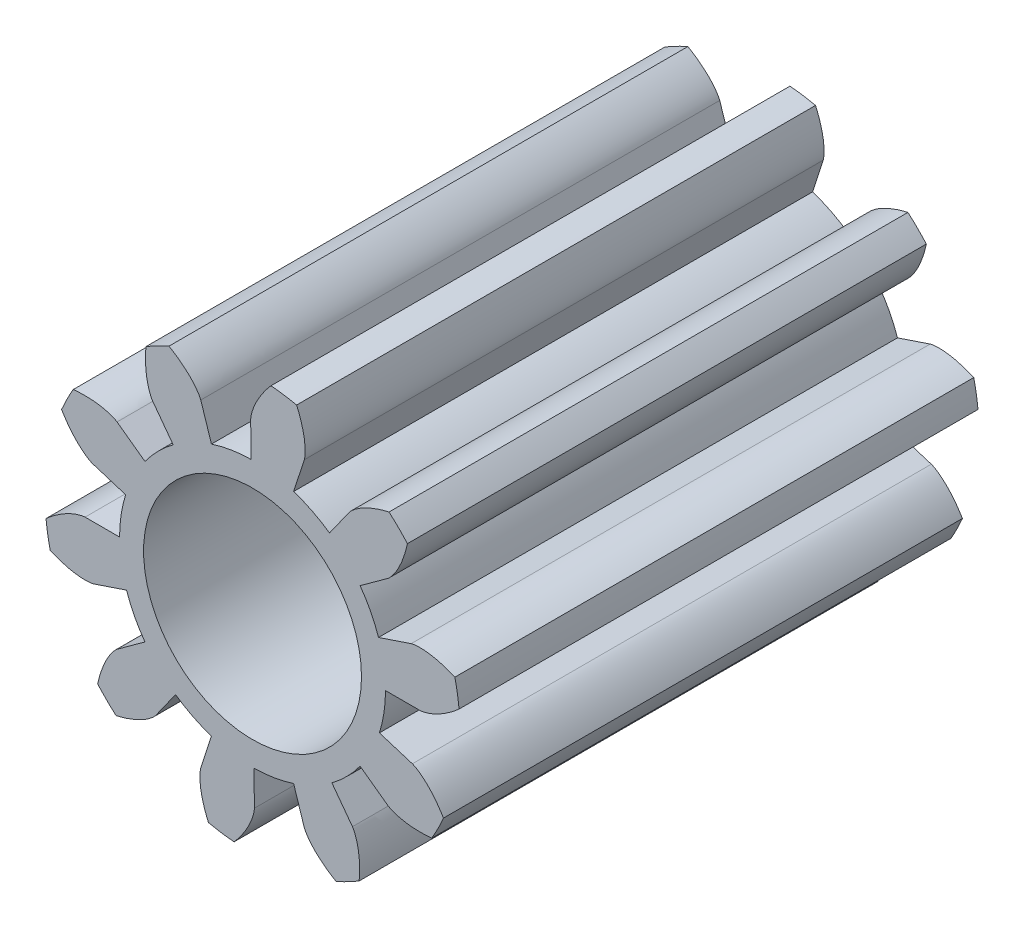
SolidWorks part; units mm, degrees
note: '?' marks a value the reader was unsure of. The reader was unsure of these and kept them because the rebuilt part matched: shared geometry of "Sketch1<7>".
material "AISI 4130 Steel, normalized at 870C"
ref_plane "Front Plane" through (0, 0, 0) normal (0, 0, 1) x (1, 0, 0)
ref_plane "Top Plane" through (0, 0, 0) normal (0, 1, 0) x (1, 0, 0)
ref_plane "Right Plane" through (0, 0, 0) normal (1, 0, 0) x (0, 0, -1)
sketch "Sketch1" plane through (0, 0, 0) normal (0, 0, 1) x (1, 0, 0)
  line L0 (6.1477, 0) -> (4.8806, 0)
  line L1 (7.5195, 1.2338) -> (-7.5195, -1.2338)
  line L2 (0, 0) -> (6.3499, 0.0352) construction
  circle A0 centre (0, 0) radius 6.1477 construction
  circle A1 centre (0, 0) radius 7.62
  circle A2 centre (0, 0) radius 4.8806
  circle A3 centre (0, 0) radius 6.35 construction
  spline S0 degree 4 poles (6.1477, 0) (6.1523, 0.0001) (6.165, 0.0007) (6.189, 0.0029) (6.2281, 0.0082) (6.2775, 0.0175) (6.341, 0.0322) (6.415, 0.053) (6.4955, 0.0796) (6.5819, 0.1125) (6.6671, 0.1487) (6.7509, 0.188) (6.8333, 0.23) (6.9318, 0.2841) (7.0479, 0.3536) (7.1805, 0.4412) (7.3269, 0.548) (7.4716, 0.6647) (7.6101, 0.7858) (7.7452, 0.9151) (7.8725, 1.0451) (7.9994, 1.187) (8.1138, 1.3213) (8.2358, 1.479) (8.3325, 1.6083) (8.453, 1.7861) (8.5222, 1.8932) (8.6005, 2.0209) (8.634, 2.0789) (8.6547, 2.1145) knots 0 0 0 0 0 0.005377 0.015084 0.028532 0.04661 0.064855 0.092111 0.119476 0.146842 0.174209 0.201575 0.228941 0.256307 0.307035 0.361767 0.4165 0.471232 0.525964 0.580697 0.635429 0.690161 0.744894 0.799626 0.854358 0.909091 0.954545 1 1 1 1 1 construction
  spline S1 degree 4 poles (6.1477, 0) (6.1523, 0.0001) (6.165, 0.0007) (6.189, 0.0029) (6.2281, 0.0082) (6.2775, 0.0175) (6.341, 0.0322) (6.415, 0.053) (6.4955, 0.0796) (6.5819, 0.1125) (6.6671, 0.1487) (6.7509, 0.188) (6.8333, 0.23) (6.9318, 0.2841) (7.0479, 0.3536) (7.1805, 0.4412) (7.3269, 0.548) (7.4716, 0.6647) (7.6101, 0.7858) (7.7452, 0.9151) (7.8725, 1.0451) (7.9994, 1.187) (8.1138, 1.3213) (8.2358, 1.479) (8.3325, 1.6083) (8.4269, 1.7475) (8.4721, 1.8161) (8.4948, 1.8515) knots 0 0 0 0 0 0.005377 0.015084 0.028532 0.04661 0.064855 0.092111 0.119476 0.146842 0.174209 0.201575 0.228941 0.256307 0.307035 0.361767 0.4165 0.471232 0.525964 0.580697 0.635429 0.690161 0.744894 0.799626 0.854358 0.909091 0.909091 0.909091 0.909091 0.909091
  dimension "D1" = 12.2955
  dimension "D2" = 15.24
  dimension "D5" = 12.7
  dimension "D3" = 9.7612
  dimension "D4" = 9
extrude "Boss-Extrude3" add sketch "Sketch1" along normal mid plane 19.05 contours A2 S1 A1 L1
sketch "Sketch5" plane through (0, 0, 0) normal (0, 0, 1) x (1, 0, 0)
  circle A0 centre (0, 0) radius 6.35
  dimension "D1" = 12.7
surface "Pitch Diameter Surface" sketch "Sketch5" parameters "D1"=2.54
mirror "Mirror2" about plane through (0, 0, 9.525) normal (0.1619, -0.9868, 0) of "Boss-Extrude3"
pattern_circular "CirPattern8" count 10 over 360 about axis through (0, 0, -1.27) along (0, 0, 1) of "Mirror2" reverse direction yes
extrude "Boss-Extrude4" add sketch "Sketch1<7>" along normal mid plane 19.05 contours A2
sketch "Sketch1<7>" plane through (0, 0, 0) normal (0, 0, 1) x (1, 0, 0) same geometry as "Sketch1"
ref_axis "Axis1" through (0, 0, -1.7463) along (0, 0, 1)?
sketch "Sketch6" plane through (0, 0, 0) normal (0, 0, 1) x (1, 0, 0)
  circle A0 centre (0, 0) radius 4
  dimension "D1" = 8
extrude "Cut-Extrude1" cut sketch "Sketch6" against normal through all both and the other way through all
equation "\"d\"= int ( ( \"N\" / \"P\" ) * 1000 ) / 1000'Pitch diameter"
equation "\"N\"= 10'Number of teeth"
equation "\"bl\"= .05mm'Backlash"
equation "\"pa\"= 14.5'Pressure angle (deg)"
equation "\"pc\"= ( 3.1415 * \"d\" ) / \"N\"\t'Circular pitch"
equation "\"m\"= \"d\" / \"N\"\t\t\t'module"
equation "\"P\"= 20'Diametral pitch"
equation "\"a\"= 1/\"P\"\t\t\t'Addendum distance"
equation "\"b\"= 1.157 / \"P\"'Dedendum distance"
equation "\"rb\"= (\"d\"/2)*cos(\"pa\")\t\t'base circle radius"
equation "\"cp\"= 3.1415/\"P\"\t\t'Circular pitch"
equation "\"t\"= ( 1.5708 / \"P\" )'tooth tickness"
equation "\"c\"= \"b\" - \"a\"'Clearance"
equation "\"facewidth\"= .75'face width"
equation "\"rbd\"= \"rb\" * 2'base circle diameter"
equation "\"D1@Sketch1\"=\"rbd\""
equation "\"D2@Sketch1\"= \"d\" + ( \"a\" * 2 )"
equation "\"D4@Sketch1\"= ( ( \"t\" / 2 ) / ( \"d\" / 2 ) ) * ( 180 / 3.1415 )"
equation "\"D1@Boss-Extrude3\"=\"facewidth\""
equation "\"D1@CirPattern8\"=\"N\""
equation "\"D5@Sketch1\"=\"d\""
equation "\"shaftdia\"= 8mm"
equation "\"D1@Sketch5\"=\"d\""
equation "\"BD\"= .7"
equation "\"BW\"= .5"
equation "\"Mid Plane Boss\"= 1"
equation "\"Hex Cut\"= 1"
equation "\"Teeth Chamfer\"= 1"
equation "\"Round Cut\"= 0"
equation "\"Round Cut Chamfer\"= 1"
equation "\"Keyway Cut\"= 0"
equation "\"Releaf Cut\"= 1"
equation "\"RD\"= .813'Releaf Outer Diameter"
equation "\"RID\"= .625'Releaf Inter Diameter"
equation "\"wd\"= ( 2.157 / \"P\" )"
equation "\"D1@Boss-Extrude4\"=\"facewidth\""
equation "\"Versa Keys and Screw Holes\"= 1"
equation "\"32 DP CIM Boss\"= 1"
equation "\"D3@Sketch1\"= \"d\" - ( \"b\" * 2 )"
equation "\"Ball Shifter Boss\"=1"
